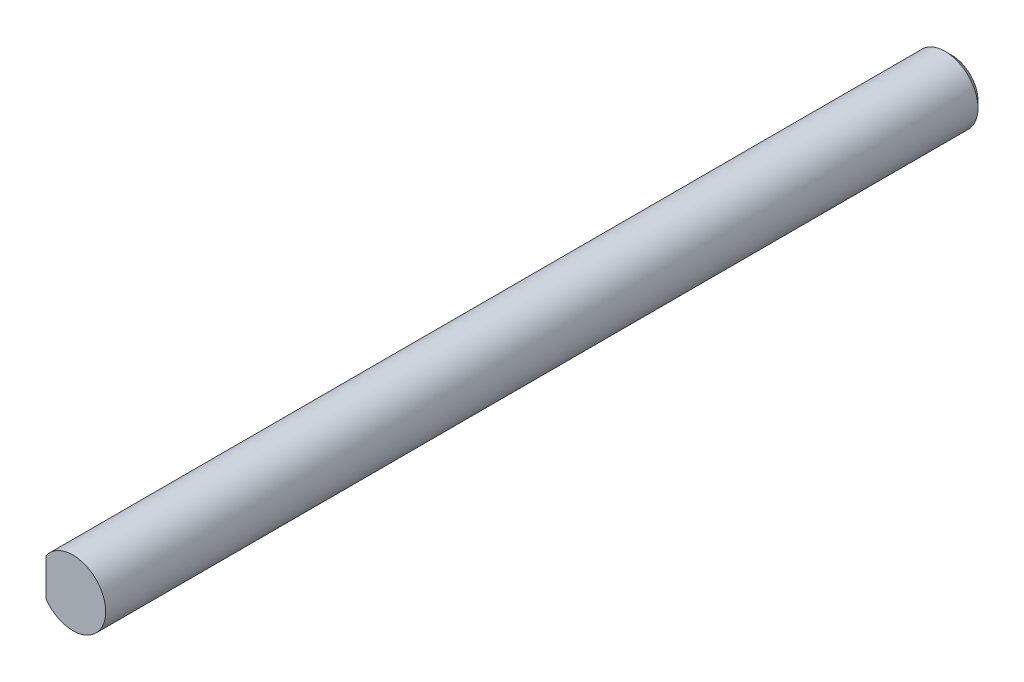
SolidWorks part; units mm, degrees
material "Acero aleado"
ref_plane "Alzado" through (0, 0, 0) normal (0, 0, 1) x (1, 0, 0)
ref_plane "Planta" through (0, 0, 0) normal (0, 1, 0) x (1, 0, 0)
ref_plane "Vista lateral" through (0, 0, 0) normal (1, 0, 0) x (0, 0, -1)
sketch "Croquis1" plane through (0, 0, 0) normal (0, 0, 1) x (1, 0, 0)
  circle A0 centre (0, 0) radius 2.5
  dimension "D1" = 5
extrude "Saliente-Extruir1" add sketch "Croquis1" along normal blind 67
sketch "Sketch1" plane through (0, 0, 67) normal (0, 0, 1) x (1, 0, 0)
  line L0 (-2.05, 1.4309) -> (-2.05, -1.4309)
  line L1 (-2.05, 0) -> (2.5, 0) construction
  arc A2 (-2.05, 1.4309) -> (-2.05, -1.4309) centre (0, 0) ccw
  circle A3 centre (0, 0) radius 2.5 construction
  dimension "D1" = 4.55
extrude "Cut-Extrude1" cut sketch "Sketch1" against normal blind 15
chamfer "Chamfer1" distance 0.5 angle 45 1 edges at (2.5, 0, 0)
